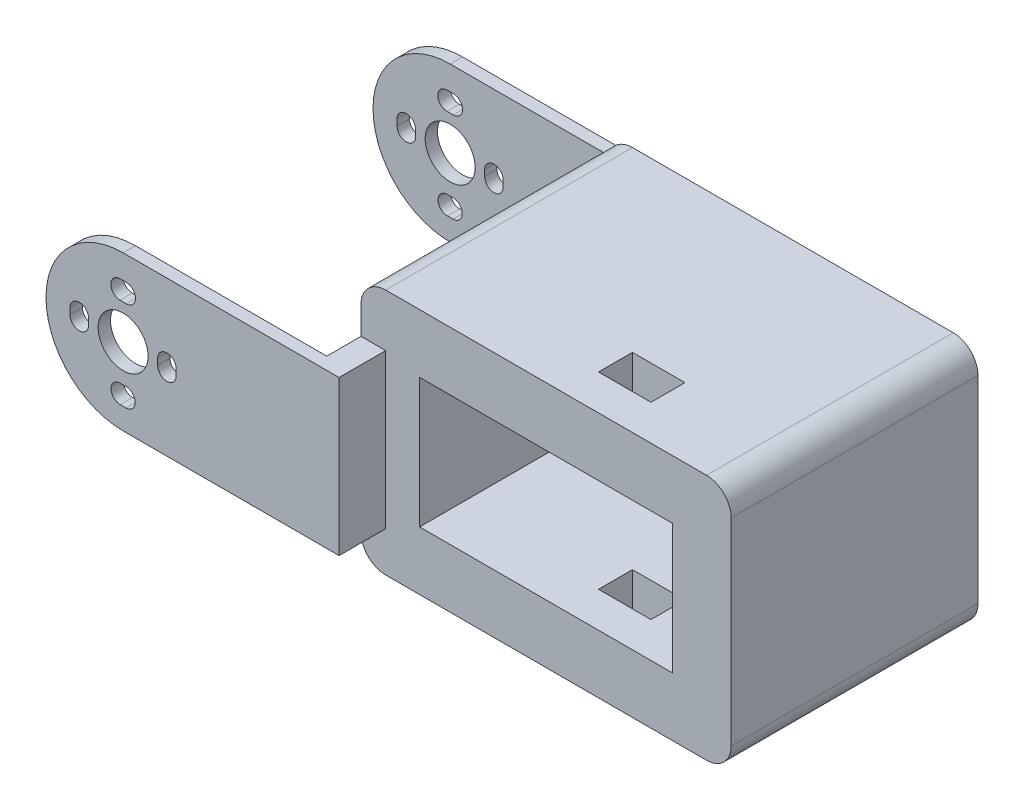
SolidWorks part; units mm, degrees
ref_plane "前基準面" through (0, 0, 0) normal (0, 0, 1) x (1, 0, 0)
ref_plane "上基準面" through (0, 0, 0) normal (0, 1, 0) x (1, 0, 0)
ref_plane "右基準面" through (0, 0, 0) normal (1, 0, 0) x (0, 0, -1)
sketch "Sketch1" plane through (0, 0, 0) normal (0, 0, 1) x (1, 0, 0)
  line L0 (-29.0958, -5.1361) -> (30.9042, -5.1361) construction
  line L1 (-19.5958, 5.3639) -> (21.4042, 5.3639)
  line L2 (-19.5958, 5.3639) -> (-19.5958, -15.6361)
  line L3 (-19.5958, -15.6361) -> (21.4042, -15.6361)
  line L4 (21.4042, 5.3639) -> (21.4042, -15.6361)
  line L5 (-29.0958, 14.8639) -> (30.9042, 14.8639)
  line L6 (-29.0958, 14.8639) -> (-29.0958, -25.1361)
  line L7 (-29.0958, -25.1361) -> (30.9042, -25.1361)
  line L8 (30.9042, 14.8639) -> (30.9042, -25.1361)
  line L9 (0.9042, 14.8639) -> (0.9042, -25.1361) construction
  line L10 (21.4042, -5.1361) -> (-19.5958, -5.1361) construction
  line L11 (0.9042, 5.3639) -> (0.9042, -15.6361) construction
  point P16 (0.9042, -5.1361)
  point P17 (0.9042, -5.1361)
  dimension "D1" = 21
  dimension "D2" = 41
  dimension "D3" = 60
  dimension "D4" = 40
extrude "Boss-Extrude1" add sketch "Sketch1" along normal blind 40
sketch "Sketch2" plane through (0, 0, 40) normal (0, 0, 1) x (1, 0, 0)
  line L0 (-19.5958, -5.1361) -> (-29.0958, -5.1361) construction
  line L2 (-19.5958, 5.3639) -> (-19.5958, -15.6361) construction
  line L3 (-29.0958, 14.8639) -> (-29.0958, -25.1361) construction
  line L4 (-25.0958, -6.1361) -> (-29.4032, -6.1361) construction
  line L5 (-29.0958, 6.3639) -> (-25.0958, 6.3639)
  line L6 (-29.0958, 6.3639) -> (-29.0958, -18.6361)
  line L7 (-29.0958, -18.6361) -> (-25.0958, -18.6361)
  line L8 (-25.0958, 6.3639) -> (-25.0958, -18.6361)
  dimension "D1" = 25
  dimension "D2" = 4
extrude "Boss-Extrude2" add sketch "Sketch2" along normal blind 5.55
extrude "Boss-Extrude3" add sketch "Sketch2<2>" against normal blind 45.55
sketch "Sketch2<2>" plane through (0, 0, 40) normal (0, 0, 1) x (1, 0, 0) same geometry as "Sketch2"
sketch "Sketch3" plane through (0, 0, 45.55) normal (0, 0, 1) x (1, 0, 0)
  line L0 (-60.5958, 0.9639) -> (-59.5958, 0.9639) construction
  line L1 (-25.0958, 6.3639) -> (-60.0958, 6.3639)
  line L2 (-25.0958, 6.3639) -> (-25.0958, -18.6361)
  line L3 (-25.0958, -18.6361) -> (-60.0958, -18.6361)
  line L4 (-60.0958, 6.3639) -> (-60.0958, -18.6361)
  line L5 (-60.5958, 2.4639) -> (-59.5958, 2.4639)
  line L6 (-60.5958, -0.5361) -> (-59.5958, -0.5361)
  line L7 (-60.0958, 6.3639) -> (-60.0958, -18.6361) construction
  line L8 (-60.5559, -13.6762) -> (-59.6357, -13.6762) construction
  line L9 (-60.5559, -12.1762) -> (-59.6357, -12.1762)
  line L10 (-60.5559, -15.1762) -> (-59.6357, -15.1762)
  line L11 (-60.0958, -6.1361) -> (-72.5958, -6.1361) construction
  line L12 (-67.1958, -5.6361) -> (-67.1958, -6.6361) construction
  line L15 (-65.6958, -5.6361) -> (-65.6958, -6.6361)
  line L16 (-68.6958, -5.6361) -> (-68.6958, -6.6361)
  line L17 (-52.9958, -5.6361) -> (-52.9958, -6.6361) construction
  line L18 (-51.4958, -5.6361) -> (-51.4958, -6.6361)
  line L19 (-54.4958, -5.6361) -> (-54.4958, -6.6361)
  line L20 (-60.0958, -6.1361) -> (-25.0958, -6.1361) construction
  arc A0 (-60.0958, 6.3639) -> (-60.0958, -18.6361) centre (-60.0958, -6.1361) ccw
  circle A1 centre (-60.0958, -6.1361) radius 4.05
  arc A3 (-60.5958, 2.4639) -> (-60.5958, -0.5361) centre (-60.5958, 0.9639) ccw
  arc A4 (-59.5958, -0.5361) -> (-59.5958, 2.4639) centre (-59.5958, 0.9639) ccw
  arc A5 (-60.5559, -12.1762) -> (-60.5559, -15.1762) centre (-60.5559, -13.6762) ccw
  arc A6 (-59.6357, -15.1762) -> (-59.6357, -12.1762) centre (-59.6357, -13.6762) ccw
  arc A9 (-65.6958, -5.6361) -> (-68.6958, -5.6361) centre (-67.1958, -5.6361) ccw
  arc A10 (-68.6958, -6.6361) -> (-65.6958, -6.6361) centre (-67.1958, -6.6361) ccw
  arc A11 (-51.4958, -5.6361) -> (-54.4958, -5.6361) centre (-52.9958, -5.6361) ccw
  arc A12 (-54.4958, -6.6361) -> (-51.4958, -6.6361) centre (-52.9958, -6.6361) ccw
  point P9 (-60.0958, 0.9639)
  point P14 (-58.0958, 0.9639)
  point P15 (-62.0958, 0.9639)
  point P19 (-60.0958, -13.6762)
  point P25 (-67.1958, -6.1361)
  point P31 (-67.1958, -4.1361)
  point P32 (-67.1958, -8.1361)
  point P34 (-65.6958, -6.1361)
  point P37 (-52.9958, -6.1361)
  point P42 (-52.9958, -4.1361)
  point P43 (-52.9958, -8.1361)
  line M15 (-29.0958, 6.3639) -> (-29.0958, -18.6361)
  line M16 (-29.0958, -18.6361) -> (-25.0958, -18.6361)
  line M17 (-25.0958, -18.6361) -> (-25.0958, 6.3639)
  line M18 (-25.0958, 6.3639) -> (-29.0958, 6.3639)
  dimension "D2" = 4
  dimension "D10" = 5.6
  dimension "D9" = 4
  dimension "D1" = 35
  dimension "D3" = 3
  dimension "D4" = 5.6
  dimension "D5" = 25
  dimension "D6" = 6.0402
  dimension "D7" = 0
  dimension "D8" = 3
  dimension "D11" = 5.6
  dimension "D12" = 3
  dimension "D13" = 4
extrude "Boss-Extrude6" add sketch "Sketch3" along normal blind 2 contours A5 L9 L4 A1 L6 A3 L5 A0 L10 A10 L16 A9 L15 | A6 L10 L4 L3 L1 L5 A4 L6 A1 L9 A12 L19 A11 L18 M15 | M18 M15 M16 M17 region at (-27.0958, -6.1361, 45.55) region at (-43.7932, -6.1343, 45.55) region at (-60.3753, 4.4139, 45.55)
extrude "Boss-Extrude7" add sketch "Sketch3<8>" against normal blind 53 contours A5 L9 L4 A1 L6 A3 L5 A0 L10 A10 L16 A9 L15 | A6 L10 L4 L3 L1 L5 A4 L6 A1 L9 A12 L19 A11 L18 M15 | M18 M15 M16 M17 region at (-27.0958, -6.1361, 45.55) region at (-43.7932, -6.1343, 45.55) region at (-60.3753, 4.4139, 45.55)
sketch "Sketch3<8>" plane through (0, 0, 45.55) normal (0, 0, 1) x (1, 0, 0) same geometry as "Sketch3"
extrude "Cut-Extrude1" cut sketch "Sketch3<11>" against normal blind 51 contours A6 L10 L4 L3 L1 L5 A4 L6 A1 L9 A12 L19 A11 L18 M15 | A5 L9 L4 A1 L6 A3 L5 A0 L10 A10 L16 A9 L15 region at (-43.7932, -6.1343, 45.55) region at (-60.3753, 4.4139, 45.55)
sketch "Sketch3<11>" plane through (0, 0, 45.55) normal (0, 0, 1) x (1, 0, 0) same geometry as "Sketch3"
sketch "草圖1" plane through (0, 14.8639, 0) normal (0, 1, 0) x (1, 0, 0)
  line L0 (30.9042, -40) -> (30.9042, 0) construction
  line L1 (12.1542, -34.25) -> (3.6542, -34.25)
  line L2 (12.1542, -34.25) -> (12.1542, -28.75)
  line L3 (12.1542, -28.75) -> (3.6542, -28.75)
  line L4 (3.6542, -34.25) -> (3.6542, -28.75)
  line L5 (30.9042, -40) -> (-29.0958, -40) construction
  dimension "D1" = 8.5
  dimension "D2" = 5.5
  dimension "D3" = 18.75
  dimension "D4" = 5.75
extrude "除料-伸長1" cut sketch "草圖1" against normal blind 40
fillet "圓角2" radius 4 1 edges at (-29.0958, -25.1361, 20) type face fillet first side face at (7.9042, -25.1361, 31.5) second side face at (-29.0958, -5.8027, 20.0167)
fillet "圓角3" radius 4 1 edges at (30.9042, -25.1361, 20) type face fillet first side face at (7.9042, -25.1361, 31.5) second side face at (30.9042, -5.1361, 20)
fillet "圓角4" radius 4 1 edges at (30.9042, 14.8639, 20) type face fillet first side face at (30.9042, -3.1361, 20) second side face at (7.9042, 14.8639, 31.5)
fillet "圓角5" radius 4 1 edges at (-29.0958, 14.8639, 20) type face fillet first side face at (7.9042, 14.8639, 31.5) second side face at (-29.0958, -5.1361, 20.0167)
